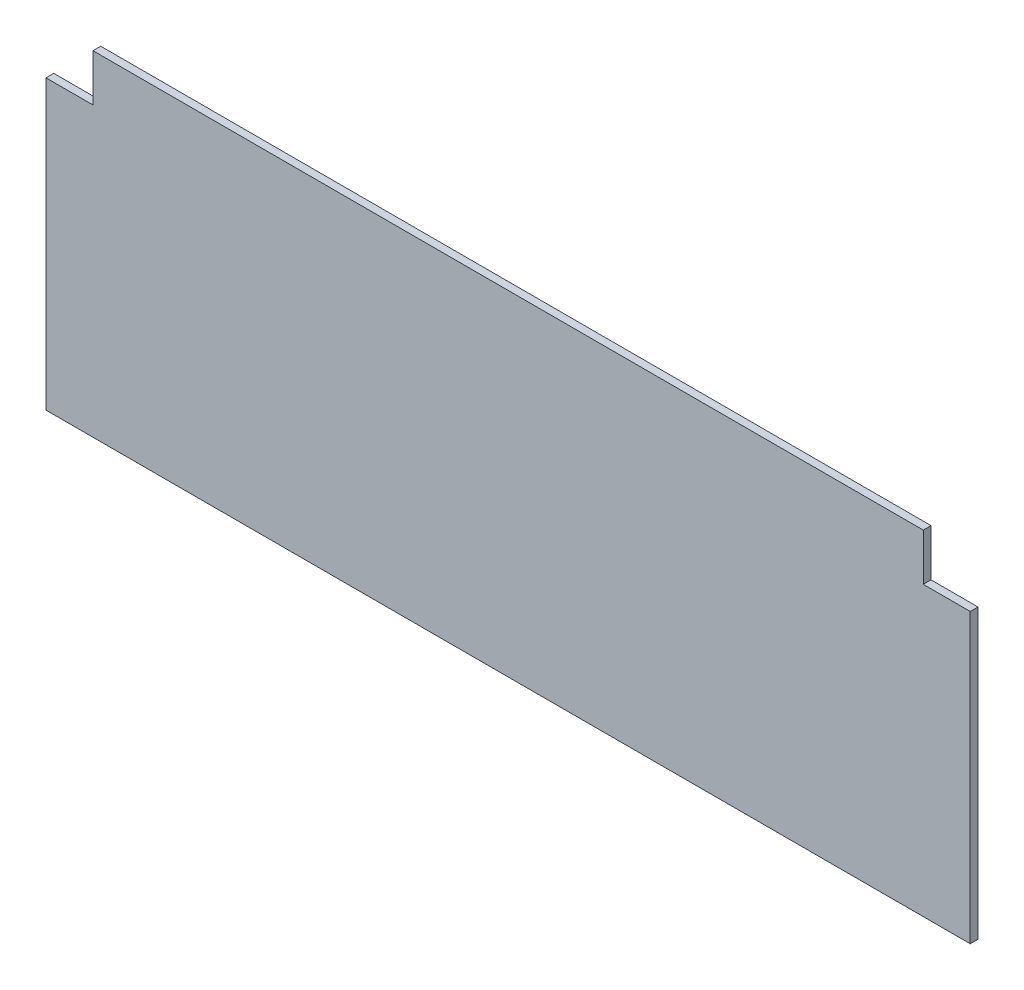
SolidWorks part; units mm, degrees
material "Balsa"
ref_plane "Front Plane" through (0, 0, 0) normal (0, 0, 1) x (1, 0, 0)
ref_plane "Top Plane" through (0, 0, 0) normal (0, 1, 0) x (1, 0, 0)
ref_plane "Right Plane" through (0, 0, 0) normal (1, 0, 0) x (0, 0, -1)
sketch "Sketch1" plane through (0, 0, 0) normal (0, 0, 1) x (1, 0, 0)
  line L0 (393.4, -162.3043) -> (393.4, -39.8043)
  line L1 (393.4, -39.8043) -> (0, -39.8043) construction
  line L2 (0, -39.8043) -> (0, -162.3043)
  line L3 (0, -162.3043) -> (393.4, -162.3043)
  line L4 (0, -138.3774) -> (0, -39.8043) construction
  line L5 (373.4, -39.8043) -> (20, -39.8043) construction
  line L6 (373.4, -39.8043) -> (373.4, -19.8043)
  line L7 (373.4, -19.8043) -> (20, -19.8043)
  line L8 (20, -39.8043) -> (20, -19.8043)
  line L9 (373.4, -39.8043) -> (20, -19.8043) construction
  line L10 (373.4, -19.8043) -> (20, -39.8043) construction
  line L12 (0, -162.3043) -> (-3.3, -162.3043) construction
  line L13 (20.7, -19.8043) -> (372.7, -19.8043) construction
  line L14 (393.4, -39.8043) -> (393.4, -138.3812) construction
  line L19 (393.4, -39.8043) -> (373.4, -39.8043)
  line L20 (0, -39.8043) -> (20, -39.8043)
  point P12 (196.7, -29.8043)
  dimension "D1" = 20
  dimension "D2" = 20
  dimension "D3" = 20
extrude "Boss-Extrude1" add sketch "Sketch1" against normal blind 3.3 contours L2 L3 L0 L1 | L8 L1 L6 L7 region at (196.7, -91.941, 0)
